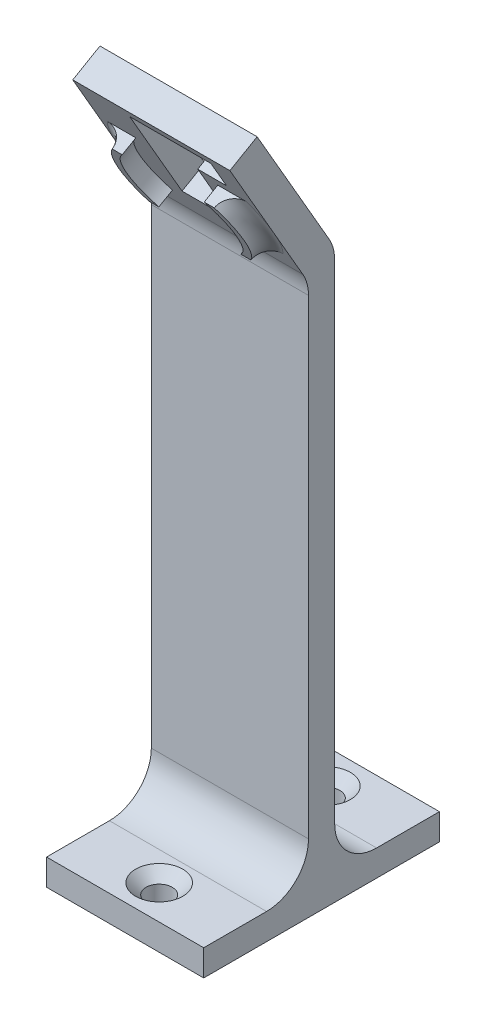
SolidWorks part; units mm, degrees
ref_plane "Front Plane" through (0, 0, 0) normal (0, 0, 1) x (1, 0, 0)
ref_plane "Top Plane" through (0, 0, 0) normal (0, 1, 0) x (1, 0, 0)
ref_plane "Right Plane" through (0, 0, 0) normal (1, 0, 0) x (0, 0, -1)
sketch "Sketch1" plane through (0, 0, 0) normal (0, 1, 0) x (1, 0, 0)
  line L1 (-15, 22.5) -> (15, 22.5)
  line L2 (-15, 22.5) -> (-15, -22.5)
  line L3 (-15, -22.5) -> (15, -22.5)
  line L4 (15, 22.5) -> (15, -22.5)
  line L5 (-15, 22.5) -> (15, -22.5) construction
  line L6 (-15, -22.5) -> (15, 22.5) construction
  point P0 (0, 0)
  dimension "D1" = 45
  dimension "D2" = 30
extrude "Boss-Extrude1" add sketch "Sketch1" along normal blind 5
sketch "Sketch2" plane through (0, 5, 0) normal (0, 1, 0) x (1, 0, 0)
  line L0 (15, -22.5) -> (15, 22.5) construction
  line L1 (-15, 2.5) -> (15, 2.5)
  line L2 (-15, 2.5) -> (-15, -2.5)
  line L3 (-15, -2.5) -> (15, -2.5)
  line L4 (15, 2.5) -> (15, -2.5)
  line L5 (-15, 2.5) -> (15, -2.5) construction
  line L6 (-15, -2.5) -> (15, 2.5) construction
  point P0 (0, 0)
  dimension "D1" = 5
extrude "Boss-Extrude2" add sketch "Sketch2" along normal blind 100
sketch "Sketch3" plane through (15, 0, 0) normal (1, 0, 0) x (0, 0, -1)
  line L0 (-2.5, 105) -> (-17.5, 130.9808)
  line L1 (-17.5, 130.9808) -> (-12.3038, 133.9808)
  line L2 (-12.3038, 133.9808) -> (2.5, 108.3397)
  line L3 (-2.5, 105) -> (2.5, 105)
  line L4 (2.5, 105) -> (2.5, 108.3397)
  line L5 (1.6854, 105) -> (-49998.3146, 105) construction
  dimension "D1" = 6
  dimension "D2" = 30
  dimension "D3" = 60
extrude "Boss-Extrude3" add sketch "Sketch3" against normal up to surface (30 mm away) up to face at (-15, 41.25, -2.5)
fillet "Fillet1" radius 8 4 edges at (0, 105, 2.5) (0, 108.3397, -2.5)
sketch "Sketch4" plane through (0, 5, 0) normal (0, 1, 0) x (1, 0, 0)
  line L0 (0, 0) -> (0, 50000) construction
  line L1 (0, 0) -> (50000, 0) construction
  circle A0 centre (0, 16) radius 2.5
  circle A1 centre (0, -16) radius 2.5
  dimension "D2" = 5
  dimension "D1" = 32
extrude "Cut-Extrude1" cut sketch "Sketch4" against normal through all
chamfer "Chamfer1" distance 2 angle 45 2 edges at (0, 5, -13.5) (0, 5, 18.5)
sketch "Sketch5" plane through (0, 28.1675, -48.7875) normal (0, 0.5, -0.866) x (1, 0, 0)
  line L0 (0, -106.014) -> (0, 49893.986) construction
  line L2 (13, -120.9506) -> (-13, -120.9506)
  line L3 (13, -120.9506) -> (13, -95.9506)
  line L4 (13, -95.9506) -> (-13, -95.9506)
  line L5 (-15, -122.1827) -> (15, -122.1827) construction
  line L6 (15, -108.4506) -> (-49985, -108.4506) construction
  line L7 (15, -94.7186) -> (15, -122.1827) construction
  line L8 (-15, -122.1827) -> (-15, -94.7186) construction
  line L9 (-13, -120.9506) -> (-13, -95.9506)
  line L10 (13, -120.9506) -> (-13, -95.9506) construction
  line L11 (13, -95.9506) -> (-13, -120.9506) construction
  point P0 (0, -108.4506)
  point P8 (0, -122.1827)
  point P13 (15, -108.4506)
  point P16 (-15, -108.4506)
  dimension "D1" = 26
  dimension "D2" = 25
extrude "Cut-Extrude2" cut sketch "Sketch5" against normal blind 1
sketch "Sketch8" plane through (0, 25.1675, -43.5913) normal (0, -0.5, 0.866) x (1, 0, 0)
  line L0 (-4, 105.4506) -> (49996, 105.4506) construction
  line L1 (-4, 109.4506) -> (-4, 101.4506) construction
  line L3 (0, 93.1353) -> (0, -49906.8647) construction
  line L4 (4, 109.4506) -> (-4, 109.4506) construction
  line L5 (-4, 101.4506) -> (4, 101.4506) construction
  line L6 (-9.7468, 112.4506) -> (-7.8262, 112.4506)
  line L7 (-9.7468, 98.4506) -> (-7.8262, 98.4506)
  line L9 (7.8262, 98.4506) -> (9.7468, 98.4506)
  line L10 (7.8262, 112.4506) -> (9.7468, 112.4506)
  arc A0 (-9.7468, 112.4506) -> (-9.7468, 98.4506) centre (0, 105.4506) ccw
  arc A1 (-7.8262, 112.4506) -> (-7.8262, 98.4506) centre (0, 105.4506) ccw
  arc A2 (9.7468, 98.4506) -> (9.7468, 112.4506) centre (0, 105.4506) ccw
  arc A3 (7.8262, 98.4506) -> (7.8262, 112.4506) centre (0, 105.4506) ccw
  point P4 (-4, 105.4506)
  point P12 (0, 109.4506)
  point P15 (0, 101.4506)
  dimension "D1" = 24
  dimension "D2" = 21
  dimension "D3" = 14
extrude "Boss-Extrude5" add sketch "Sketch8" along normal blind 3
sketch "Sketch6" plane through (0, 25.1675, -43.5913) normal (0, -0.5, 0.866) x (1, 0, 0)
  line L0 (-4, 101.4506) -> (4, 101.4506) construction
  line L1 (-5, 100.4506) -> (5, 100.4506)
  line L2 (-5, 100.4506) -> (-5, 120.4506)
  line L3 (-5, 120.4506) -> (10.5, 120.4506)
  line L4 (5, 114.4506) -> (5, 100.4506)
  line L7 (10.5, 120.4506) -> (10.5, 114.4506)
  line L8 (10.5, 114.4506) -> (5, 114.4506)
  line L9 (-4, 109.4506) -> (-4, 101.4506) construction
  dimension "D1" = 10
  dimension "D2" = 20
  dimension "D3" = 1
  dimension "D4" = 1
  dimension "D5" = 6
  dimension "D6" = 5.5
extrude "Cut-Extrude3" cut sketch "Sketch6" against normal through all
sketch "Sketch7" plane through (0, 27.6675, -47.9215) normal (0, 0.5, -0.866) x (1, 0, 0)
  circle A0 centre (10.5, -105.9506) radius 0.8484
  circle A1 centre (-10.5, -118.4506) radius 0.8484
  circle A2 centre (-10.5, -118.4506) radius 1.0484 construction
  dimension "D1" = 0.2
extrude "Boss-Extrude4" add sketch "Sketch7" along normal blind 1
fillet "Fillet2" radius 3 2 edges at (12, 116.4904, 9.134) (-12, 116.4904, 9.134)
